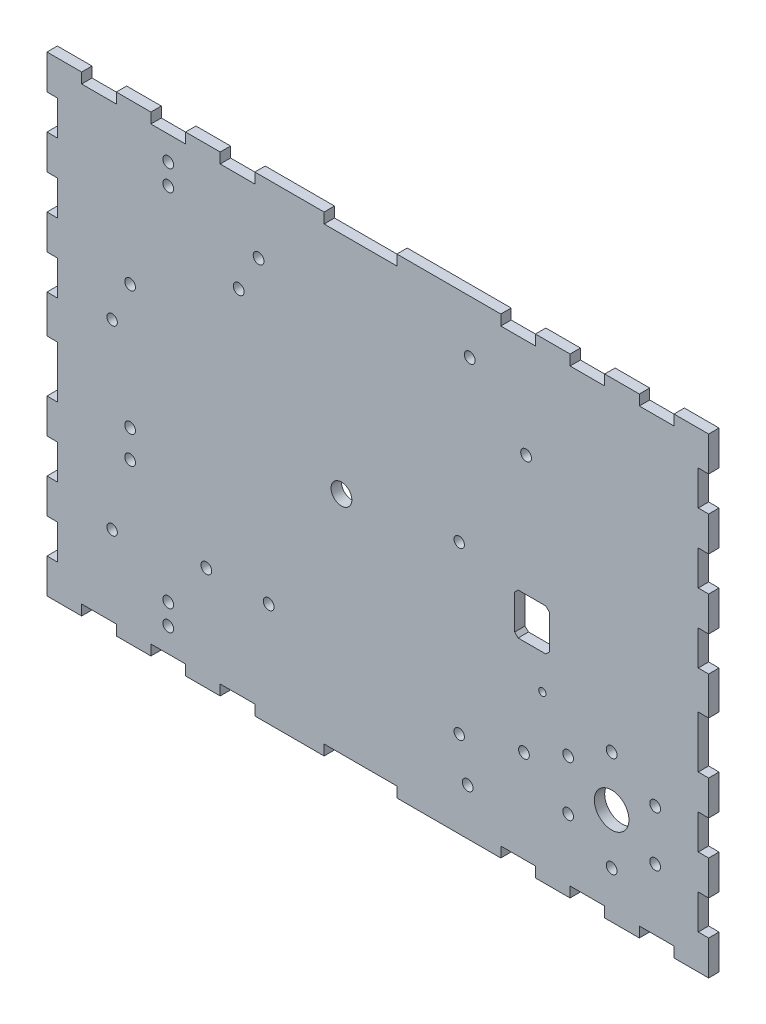
SolidWorks part; units mm, degrees
note: '?' marks a value the reader was unsure of.
ref_plane "Front Plane" through (0, 0, 0) normal (0, 0, 1) x (1, 0, 0)
ref_plane "Top Plane" through (0, 0, 0) normal (0, 1, 0) x (1, 0, 0)
ref_plane "Right Plane" through (0, 0, 0) normal (1, 0, 0) x (0, 0, -1)
sketch "Sketch2" plane through (0, 0, 0) normal (0, 0, 1) x (1, 0, 0)
  line L1 (0, 0) -> (191, 0)
  line L2 (0, 0) -> (0, 136)
  line L3 (0, 136) -> (191, 136)
  line L4 (191, 0) -> (191, 136)
  circle A0 centre (35, 16) radius 1.55 construction
  circle A1 centre (35, 10) radius 1.55 construction
  circle A2 centre (24, 46.0692) radius 1.55 construction
  circle A3 centre (24, 54.0692) radius 1.55 construction
  circle A5 centre (24, 89.9308) radius 1.55 construction
  circle A6 centre (35, 120) radius 1.55 construction
  circle A7 centre (35, 126) radius 1.55 construction
  circle A8 centre (175.5574, 35.25) radius 1.55 construction
  circle A9 centre (163, 42.5) radius 1.55 construction
  circle A10 centre (150.4426, 35.25) radius 1.55 construction
  circle A11 centre (150.4426, 20.75) radius 1.55 construction
  circle A12 centre (163, 13.5) radius 1.55 construction
  circle A13 centre (175.5574, 20.75) radius 1.55 construction
  circle A14 centre (35, 16) radius 1.55
  circle A15 centre (35, 10) radius 1.55
  circle A16 centre (24, 46.0692) radius 1.55
  circle A17 centre (24, 54.0692) radius 1.55
  circle A18 centre (18.8, 26) radius 1.5 construction
  circle A19 centre (24, 89.9308) radius 1.55
  circle A20 centre (35, 120) radius 1.55
  circle A21 centre (35, 126) radius 1.55
  circle A22 centre (175.5574, 35.25) radius 1.55
  circle A23 centre (163, 42.5) radius 1.55
  circle A24 centre (150.4426, 35.25) radius 1.55
  circle A25 centre (150.4426, 20.75) radius 1.55
  circle A26 centre (163, 13.5) radius 1.55
  circle A27 centre (175.5574, 20.75) radius 1.55
  circle A28 centre (18.8, 78.5) radius 1.5 construction
  circle A29 centre (18.8, 78.5) radius 1.5
  circle A30 centre (119, 73) radius 1.5 construction
  circle A31 centre (119, 25) radius 1.5 construction
  circle A32 centre (18.8, 26) radius 1.5
  circle A33 centre (119, 73) radius 1.5
  circle A34 centre (119, 25) radius 1.5
extrude "Boss-Extrude1" add sketch "Sketch2" along normal blind 3
ref_axis "Axis1" through (0, 68, 3) along (1, 0, 0)?
ref_plane "Plane1" through (0, 68, 0) normal (0, 1, 0) x (1, 0, 0)
ref_axis "Axis2" through (95.5, 0, 3) along (0, 1, 0)?
ref_plane "Plane2" through (95.5, 0, 0) normal (1, 0, 0) x (0, 0, -1)
sketch "Sketch3" plane through (0, 0, 3) normal (0, 0, 1) x (1, 0, 0)
  line L0 (0, 3) -> (191, 3) construction
  line L1 (0, 136) -> (0, 0) construction
  line L2 (191, 0) -> (191, 136) construction
  line L3 (0, 0) -> (191, 0) construction
  line L4 (10, 0) -> (10, 3)
  line L5 (20, 0) -> (20, 3)
  line L6 (30, 0) -> (30, 3)
  line L7 (40, 0) -> (40, 3)
  line L8 (50, 0) -> (50, 3)
  line L9 (60, 0) -> (60, 3)
  line L10 (10, 0) -> (20, 0)
  line L11 (20, 3) -> (10, 3)
  line L12 (30, 0) -> (40, 0)
  line L13 (40, 3) -> (30, 3)
  line L14 (50, 0) -> (60, 0)
  line L15 (80, 3) -> (80, 0)
  line L16 (60, 3) -> (50, 3)
  line L17 (181, 0) -> (181, 3)
  line L18 (171, 0) -> (171, 3)
  line L19 (161, 0) -> (161, 3)
  line L20 (151, 0) -> (151, 3)
  line L21 (141, 0) -> (141, 3)
  line L22 (131, 0) -> (131, 3)
  line L23 (181, 0) -> (171, 0)
  line L24 (171, 0) -> (170.9794, -0.0476)
  line L25 (171, 3) -> (181, 3)
  line L26 (181, 3) -> (181.0353, 3.2173)
  line L27 (161, 0) -> (151, 0)
  line L28 (161, 3) -> (151, 3)
  line L29 (141, 0) -> (131, 0)
  line L30 (131, 3) -> (141, 3)
  line L31 (141, 3) -> (140.9859, 2.9583)
  line L32 (101, 0) -> (101, 3)
  line L33 (80, 0) -> (101, 0)
  line L34 (101, 3) -> (80, 3)
  dimension "D6" = 20
  dimension "D1" = 3
  dimension "D2" = 10
  dimension "D4" = 10
  dimension "D7" = 30
  dimension "D3" = 6
  dimension "D5" = 6
extrude "Cut-Extrude1" cut sketch "Sketch3" against normal up to next
mirror "Mirror1" about plane through (0, 68, 0) normal (0, 1, 0) of "Cut-Extrude1"
sketch "Sketch4" plane through (0, 0, 3) normal (0, 0, 1) x (1, 0, 0)
  line L0 (3, 136) -> (3, 0) construction
  line L1 (10, 136) -> (0, 136) construction
  line L2 (0, 0) -> (10, 0) construction
  line L3 (0, 136) -> (0, 0) construction
  line L4 (0, 126) -> (3, 126)
  line L5 (0, 116) -> (3, 116)
  line L6 (0, 106) -> (3, 106)
  line L7 (0, 96) -> (3, 96)
  line L8 (0, 86) -> (3, 86)
  line L9 (0, 10) -> (3, 10)
  line L10 (0, 20) -> (3, 20)
  line L11 (0, 30) -> (3, 30)
  line L12 (0, 40) -> (3, 40)
  line L13 (0, 50) -> (3, 50)
  line L14 (0, 126) -> (0, 116)
  line L15 (3, 116) -> (3, 126)
  line L16 (0, 106) -> (0, 96)
  line L17 (3, 96) -> (3, 106)
  line L18 (0, 20) -> (0, 10)
  line L19 (3, 10) -> (3, 20)
  line L20 (0, 30) -> (0, 40)
  line L21 (3, 30) -> (3, 40)
  line L22 (0, 65) -> (3, 65)
  line L23 (0, 76) -> (3, 76)
  line L24 (0, 86) -> (0, 76)
  line L25 (3, 76) -> (3, 86)
  line L26 (0, 65) -> (0, 50)
  line L27 (3, 50) -> (3, 65)
  dimension "D1" = 3
  dimension "D2" = 10
  dimension "D4" = 10
  dimension "D6" = 15
  dimension "D3" = 6
  dimension "D5" = 5
extrude "Cut-Extrude2" cut sketch "Sketch4" against normal up to next
mirror "Mirror2" about plane through (95.5, 0, 0) normal (1, 0, 0) of "Cut-Extrude2"
sketch "Sketch6" plane through (0, 0, 3) normal (0, 0, 1) x (1, 0, 0)
  line L0 (116, 0) -> (116, 136) construction
  line L1 (101, 0) -> (131, 0) construction
  line L2 (131, 136) -> (101, 136) construction
  line L3 (191, 68) -> (85, 68) construction
  line L4 (191, 65) -> (191, 76) construction
  dimension "D1" = 106
ref_point "MountPoint-Dif"
sketch "Sketch8" plane through (0, 0, 0) normal (0, 0, -1) x (-1, 0, 0)
  circle A0 centre (-163, 28) radius 8 construction
  circle A1 centre (-163, 28) radius 8
  circle A2 centre (-163, 28) radius 5
  dimension "D1" = 10
extrude "Cut-Extrude3" cut sketch "Sketch8" against normal up to next contours A2
sketch "Sketch9" plane through (0, 0, 3) normal (0, 0, 1) x (1, 0, 0)
  circle A0 centre (85, 68) radius 3
  point P0 (85, 68)
  dimension "D1" = 6
extrude "Cut-Extrude4" cut sketch "Sketch9" against normal up to next
sketch "Sketch10" plane through (0, 0, 3) normal (0, 0, 1) x (1, 0, 0)
  circle A0 centre (61.0861, 114.9893) radius 1.55 construction
  circle A1 centre (55.3425, 104.4531) radius 1.55 construction
  circle A2 centre (138.3021, 104.3671) radius 1.55 construction
  circle A3 centre (122.0386, 120.6305) radius 1.55 construction
  circle A4 centre (64, 30) radius 1.55 construction
  circle A5 centre (46, 30) radius 1.55 construction
  circle A6 centre (137.6988, 29.7288) radius 1.55 construction
  circle A7 centre (121.4354, 13.4653) radius 1.55 construction
  circle A8 centre (61.0861, 114.9893) radius 1.55
  circle A9 centre (55.3425, 104.4531) radius 1.55
  circle A10 centre (138.3021, 104.3671) radius 1.55
  circle A11 centre (122.0386, 120.6305) radius 1.55
  circle A12 centre (64, 30) radius 1.55
  circle A13 centre (46, 30) radius 1.55
  circle A14 centre (137.6988, 29.7288) radius 1.55
  circle A15 centre (121.4354, 13.4653) radius 1.55
extrude "Cut-Extrude5" cut sketch "Sketch10" against normal up to next
sketch "Sketch11" plane through (0, 0, 3) normal (0, 0, 1) x (1, 0, 0)
  line L1 (145, 57.5) -> (135, 57.5)
  line L2 (145, 57.5) -> (145, 69.5)
  line L3 (145, 69.5) -> (135, 69.5)
  line L4 (135, 57.5) -> (135, 69.5)
  circle A0 centre (163, 42.5) radius 1.55 construction
  circle A1 centre (143, 47.5) radius 1.05
  dimension "D5" = 2.1
  dimension "D6" = 2
  dimension "D1" = 12
  dimension "D2" = 10
  dimension "D3" = 18
  dimension "D4" = 15
  dimension "D7" = 10
extrude "Cut-Extrude6" cut sketch "Sketch11" against normal up to next
chamfer "Chamfer1" distance 1 angle 45 4 edges at (135, 69.5, 1.5) (145, 69.5, 1.5) (145, 57.5, 1.5) (135, 57.5, 1.5)
